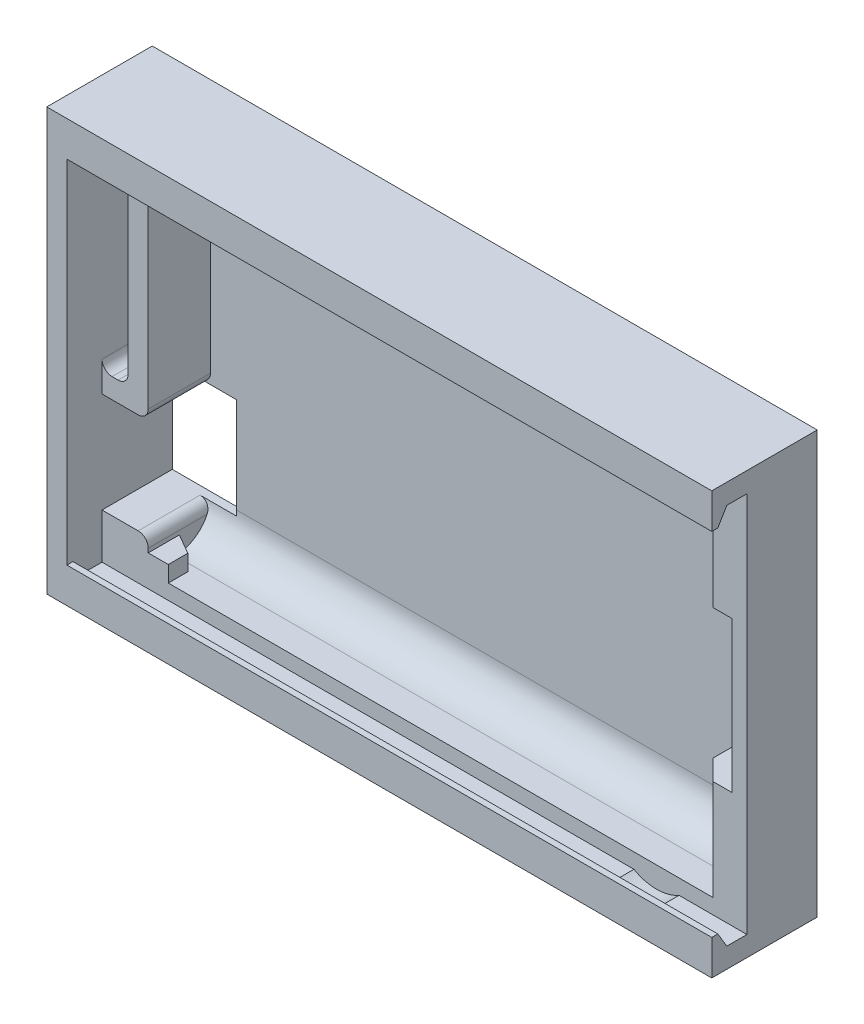
SolidWorks part; units mm, degrees
ref_plane "Front Plane" through (0, 0, 0) normal (0, 0, 1) x (1, 0, 0)
ref_plane "Top Plane" through (0, 0, 0) normal (0, 1, 0) x (1, 0, 0)
ref_plane "Right Plane" through (0, 0, 0) normal (1, 0, 0) x (0, 0, -1)
sketch "Sketch1" plane through (0, 0, 0) normal (0, 0, 1) x (1, 0, 0)
  line L1 (-26.5, 17) -> (26.5, 17)
  line L2 (-26.5, 17) -> (-26.5, -17)
  line L3 (-26.5, -17) -> (26.5, -17)
  line L4 (26.5, 17) -> (26.5, -17)
  line L5 (-26.5, 17) -> (26.5, -17) construction
  line L6 (-26.5, -17) -> (26.5, 17) construction
  point P0 (0, 0)
  dimension "D1" = 34
  dimension "D2" = 53
sketch "Sketch2" plane through (0, 0, 0) normal (0, 0, 1) x (1, 0, 0)
  line L1 (-31.7, 19) -> (32.5, 19)
  line L2 (-31.7, 19) -> (-31.7, -19)
  line L3 (-31.7, -19) -> (32.5, -19)
  line L4 (32.5, 19) -> (32.5, -19)
  line L6 (-26.5, 17) -> (-26.5, -17) construction
  line L7 (26.5, 17) -> (26.5, -17) construction
  line L8 (-26.5, -17) -> (-26.5, -19) construction
  line L9 (-26.5, 17) -> (-26.5, 19) construction
  line L10 (-26.5, 17) -> (26.5, 17) construction
  dimension "D1" = 5.2
  dimension "D2" = 6
  dimension "D3" = 2
extrude "Boss-Extrude1" add sketch "Sketch2" along normal blind 7
sketch "Sketch3" plane through (0, 0, 0) normal (1, 0, 0) x (0, 0, -1)
  line L0 (-7.3, 17) -> (-4.3, 17) construction
  line L1 (-1.3, 0) -> (-7.3, 0) construction
  line L2 (-7.3, -17) -> (-7.3, 17) construction
  line L3 (-1.3, -14) -> (-1.3, 14) construction
  line L4 (-7.3, -17) -> (-4.3, -17) construction
  line L5 (-7.8, 17.5) -> (-4.3, 17.5)
  line L6 (-0.8, -14) -> (-0.8, 14)
  line L7 (-7.8, -17.5) -> (-4.3, -17.5)
  line L8 (-7.8, -17.5) -> (-7.8, 17.5)
  arc A0 (-4.3, 17) -> (-1.3, 14) centre (-4.3, 14) cw construction
  arc A1 (-4.3, -17) -> (-1.3, -14) centre (-4.3, -14) ccw construction
  arc A2 (-4.3, 17.5) -> (-0.8, 14) centre (-4.3, 14) cw
  arc A3 (-4.3, -17.5) -> (-0.8, -14) centre (-4.3, -14) ccw
  point P6 (-12.641, 14.088)
  point P11 (-13.7836, 13.0913)
  dimension "D1" = 3
  dimension "D2" = 6
  dimension "D3" = 34
  dimension "D5" = 0.8
  dimension "D4" = 0.5
extrude "Cut-Battery" cut sketch "Sketch3" against normal mid plane 54.2
sketch "Sketch4" plane through (0, 0, 7) normal (0, 0, 1) x (1, 0, 0)
  line L1 (0, 0) -> (29.05, 0) construction
  line L2 (31, 7.5) -> (27.1, 7.5)
  line L3 (31, 7.5) -> (31, -7.5)
  line L4 (31, -7.5) -> (27.1, -7.5)
  line L7 (27.1, 7.5) -> (27.1, -7.5)
  line L8 (31, 7.5) -> (27.1, -7.5) construction
  line L9 (31, -7.5) -> (27.1, 7.5) construction
  line L10 (27.1, -14) -> (27.1, 14) construction
  line L12 (27.1, 17.5) -> (27.1, -17.5) construction
  line L13 (32.5, -19) -> (32.5, 19) construction
  point P0 (29.05, 0)
  point P9 (31.3029, -7.5)
  point P12 (27.1, -5.5675)
  dimension "D1" = 15
  dimension "D2" = 1.5
extrude "ForFinger" cut sketch "Sketch4" against normal through all
sketch "Sketch5" plane through (0, 17.5, 0) normal (0, -1, 0) x (1, 0, 0)
  line L0 (-27.1, 7) -> (-25.1, 7)
  line L1 (27.1, 7) -> (-27.1, 7) construction
  line L2 (-25.1, 7) -> (-25.1, 3.9)
  line L3 (-25.1, 3.9) -> (-27.1, 3.9)
  line L4 (-27.1, 3.9) -> (-27.1, 7)
  line L5 (-26.9, 3.8) -> (-24.9, 3.8) construction
  line L6 (-24.9, 3.8) -> (-24.9, 6.8) construction
  line L7 (-24.9, 6.8) -> (-20.5432, 6.8) construction
  line L8 (-26.9, 3.8) -> (-26.9, 0.8) construction
  line L9 (-26.9, 0.8) -> (-20.5432, 0.8) construction
  line L10 (-20.5432, 0.8) -> (-20.5432, 6.8) construction
  line L11 (-27.1, 0.8) -> (27.1, 0.8) construction
  line L12 (-27.1, 0.8) -> (-27.1, 4.3) construction
  point P9 (0, 0)
  point P14 (0, 0)
  point P15 (-20.5432, 1)
  point P18 (-24.4325, 2.1847)
  point P19 (-24.0137, 1)
  point P20 (-26.3689, 1)
  point P23 (-27.1, 3.7068)
  point P24 (-25.203, 5.2626)
  point P25 (-27.1, 4.2847)
  point P26 (-25.0697, 4.2847)
  dimension "D1" = 6
  dimension "D2" = 3
  dimension "D3" = 0.2
  dimension "D4" = 2
  dimension "D5" = 0.2
  dimension "D6" = 0.1
extrude "Boss-Extrude2" add sketch "Sketch5" along normal blind 1.6
chamfer "Chamfer1" distance 2 angle 30 1 edges at (-25.1, 16.6885, 3.9) first distance on face at (-26.1, 16.6885, 3.9)
mirror "Mirror1" about plane through (0, 0, 0) normal (0, 1, 0) of "Chamfer1", "Boss-Extrude2"
sketch "Sketch6" plane through (0, 0, 7) normal (0, 0, 1) x (1, 0, 0)
  line L1 (-31.7, -4.5) -> (-24.5, -4.5)
  line L2 (-31.7, -4.5) -> (-31.7, -14.5)
  line L3 (-31.7, -14.5) -> (-24.5, -14.5)
  line L4 (-24.5, -4.5) -> (-24.5, -14.5)
  line L7 (-26.5, -17) -> (26.5, -17) construction
  line L8 (-31.7, 19) -> (-31.7, -19) construction
  point P4 (-30.9225, -14.5)
  point P6 (-24.7465, -4.5)
  point P8 (-31.7, -9.5)
  dimension "D1" = 10
  dimension "D2" = 7.5
  dimension "D3" = 7.2
extrude "Cut-Connector" cut sketch "Sketch6" against normal through all
sketch "Sketch9" plane through (0, 0, 0) normal (0, 0, 1) x (1, 0, 0)
  line L0 (32.5, -19) -> (-31.7, -19)
  line L1 (-31.7, -19) -> (-31.7, 19)
  line L2 (-31.7, 19) -> (32.5, 19)
  line L3 (32.5, 19) -> (32.5, 21)
  line L4 (32.5, 21) -> (-33.7, 21)
  line L5 (-33.7, 21) -> (-33.7, -21)
  line L6 (-33.7, -21) -> (32.5, -21)
  line L7 (32.5, -21) -> (32.5, -19)
  line L8 (32.5, -19) -> (32.5, 19) construction
  point P13 (0, 0)
  point P14 (34.8579, -18)
  dimension "D1" = 2
  dimension "D2" = 2
extrude "Boss-Extrude3" add sketch "Sketch9" along normal offset from surface (10.5 mm away) 3.5 up to face at (-5.01, -1.9, 7) offset beyond the face yes
sketch "Sketch10" plane through (0, 0, 7) normal (0, 0, 1) x (1, 0, 0)
  line L0 (32.5, 19) -> (32.5, 21) construction
  line L1 (13.6743, 19.6) -> (23.5, 19.6) construction
  line L3 (-31.7, 19) -> (32.5, 19) construction
  line L4 (0, 0) -> (32.5, 0) construction
  line L5 (32.5, -19) -> (32.5, 19) construction
  circle A0 centre (23.5, 15.1) radius 4.5
  circle A1 centre (23.5, -15.1) radius 4.5
  dimension "D1" = 9
  dimension "D2" = 9
  dimension "D3" = 0.6
  dimension "D4" = 15.1
extrude "Cut-Latch" cut sketch "Sketch10" along normal blind 2
sketch "Sketch11" plane through (32.5, 0, 0) normal (1, 0, 0) x (0, 0, -1)
  line L0 (-10.5, 19) -> (-9, 19)
  line L1 (-10.5, 19) -> (-7, 19) construction
  line L2 (-9, 19) -> (-9.9, 17.5)
  line L3 (-9.9, 17.5) -> (-10.5, 17.5)
  line L4 (-10.5, -19) -> (-10.5, 19) construction
  line L5 (-10.5, 17.5) -> (-10.5, 19)
  line L8 (0, 0) -> (-12.817, 0) construction
  line L9 (-9.9, -17.5) -> (-10.5, -17.5)
  line L10 (-9, -19) -> (-9.9, -17.5)
  line L11 (-10.5, -19) -> (-9, -19)
  line L12 (-10.5, -17.5) -> (-10.5, -19)
  line L13 (-4.3, 17.5) -> (-7, 17.5) construction
  dimension "D1" = 0.6
  dimension "D2" = 38
  dimension "D3" = 59.036
  dimension "D4" = 1.5
extrude "Boss-Extrude4" add sketch "Sketch11" against normal up to surface (64.2 mm away) up to face at (-31.7, -4.75, 6.125)
chamfer "Chamfer2" distance 2 angle 45 2 edges at (27.1, -12.5, 7) (27.1, 12.5, 7)
fillet "Fillet2" radius 1 2 edges at (-27.1, -14.5, 3.9179) (-27.1, -4.5, 3.9)
sketch "Sketch12" plane through (0, 0, 7) normal (0, 0, 1) x (1, 0, 0)
  line L0 (-28.1, -4.5) -> (-31.7, -4.5) construction
  line L1 (-31.7, 17.5) -> (-29.1, 17.5)
  line L2 (-31.7, 17.5) -> (-31.7, -2.5)
  line L3 (-31.7, -2.5) -> (-29.1, -2.5)
  line L4 (-29.1, 17.5) -> (-29.1, -2.5)
  line L5 (-27.1, -3.5) -> (-27.1, 14) construction
  dimension "D1" = 2
  dimension "D2" = 2
  dimension "D3" = 2.6
extrude "Cut-Extrude6" cut sketch "Sketch12" against normal through all
fillet "Fillet1" radius 1 4 edges at (-29.1, 17.5, 3.5) (-31.7, 17.5, 3.5) (-31.7, -2.5, 3.5) (-29.1, -2.5, 3.5)
equation "\"D1@Cut-Battery\"=53/2+0.6"
equation "\"D2@Cut-Battery\"= 53/2+0.6"
